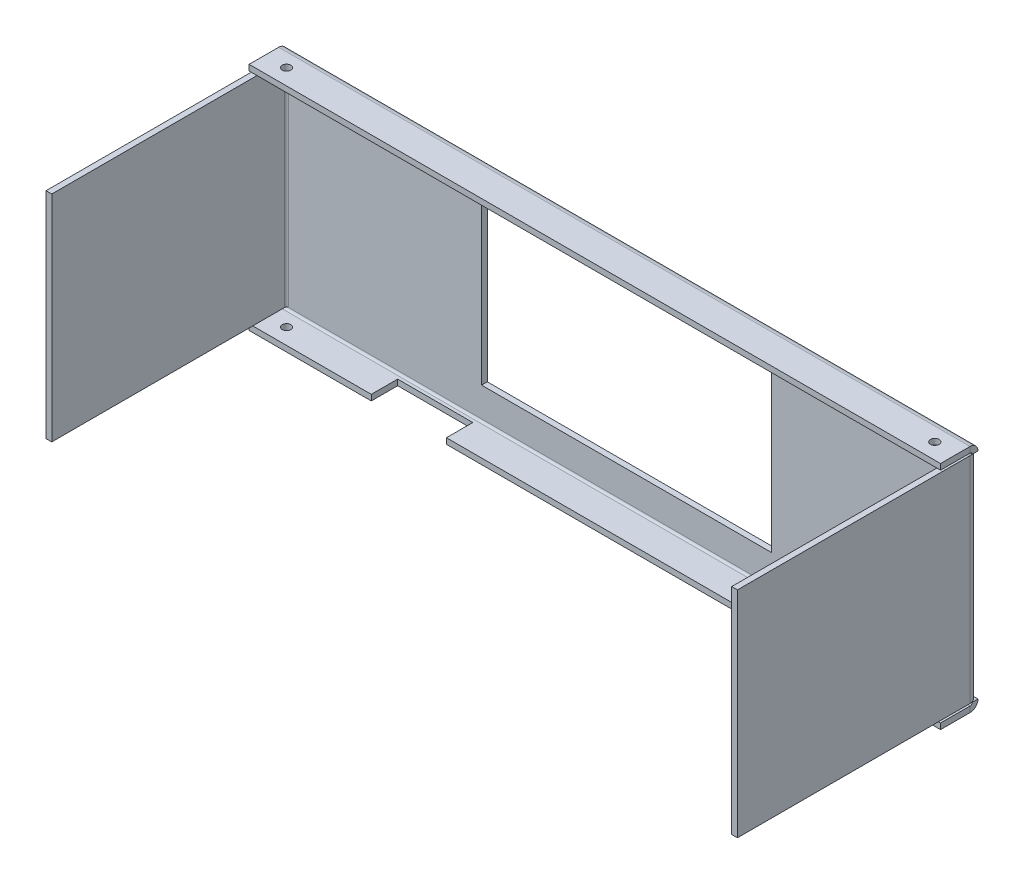
SolidWorks part; units mm, degrees
note: The reader was unsure of these and kept them because the rebuilt part matched: flange length of "Edge-Flange1", "Edge-Flange2".
ref_plane "Front Plane" through (0, 0, 0) normal (0, 0, 1) x (1, 0, 0)
ref_plane "Top Plane" through (0, 0, 0) normal (0, 1, 0) x (1, 0, 0)
ref_plane "Right Plane" through (0, 0, 0) normal (1, 0, 0) x (0, 0, -1)
sketch "Sketch1" plane through (0, 0, 0) normal (0, 0, 1) x (1, 0, 0)
  line L1 (-120, 40) -> (120, 40)
  line L2 (-120, 40) -> (-120, -40)
  line L3 (-120, -40) -> (120, -40)
  line L4 (120, 40) -> (120, -40)
  line L5 (-120, 40) -> (120, -40) construction
  line L6 (-120, -40) -> (120, 40) construction
  point P0 (0, 0)
  dimension "D1" = 240
  dimension "D2" = 80
sketch "Sketch19" plane through (0, 40, 0) normal (0, 1, 0) x (1, 0, 0)
  line L0 (120, -6.5) -> (112.5, -6.5)
  line L1 (120, 0) -> (120, -13) construction
  line L2 (112.5, 0) -> (112.5, -5.5)
  line L3 (-120, 0) -> (118, 0) construction
  circle A0 centre (112.5, -5.5) radius 1.5
  dimension "D2" = 3
  dimension "D1" = 7.5
sketch "Sketch20" plane through (0, 40, 0) normal (0, 1, 0) x (1, 0, 0)
  line L0 (0, 0) -> (0, -13) construction
  line L1 (120, -13) -> (-120, -13) construction
sketch "Sketch25" plane through (0, -38, 0) normal (0, 1, 0) x (1, 0, 0)
  line L1 (-80, 0) -> (-54, 0)
  line L2 (-80, 0) -> (-80, -13)
  line L3 (-80, -13) -> (-54, -13)
  line L4 (-54, 0) -> (-54, -13)
  dimension "D1" = 13
sketch "Sketch29" plane through (0, -38, 0) normal (0, 1, 0) x (1, 0, 0)
  line L0 (-80, -0.2803) -> (-53.9351, -0.2803)
  line L2 (-80, -0.2803) -> (-54, -0.2803)
  line L3 (-80, -0.2803) -> (-80, -13)
  line L4 (-80, -13) -> (-54, -13)
  line L5 (-54, -0.2803) -> (-54, -13)
sketch "Sketch30" plane through (0, 0, 0) normal (0, 0, 1) x (1, 0, 0)
  line L0 (-0.8839, -38) -> (-0.8839, 4.8816)
  line L1 (-80, -38) -> (-54, -38)
  line L2 (-80, -38) -> (-80, -36.4813)
  line L3 (-80, -36.4813) -> (-54, -36.4813)
  line L4 (-54, -38) -> (-54, -36.4813)
  line L6 (-51.2062, 31.9731) -> (49.4384, 31.9731)
  line L7 (-51.2062, 31.9731) -> (-51.2062, -22.2099)
  line L8 (-51.2062, -22.2099) -> (49.4384, -22.2099)
  line L9 (49.4384, 31.9731) -> (49.4384, -22.2099)
  line L10 (-51.2062, 31.9731) -> (49.4384, -22.2099) construction
  line L11 (-51.2062, -22.2099) -> (49.4384, 31.9731) construction
sketch "Sketch31" plane through (0, 0, 0) normal (0, 0, 1) x (1, 0, 0)
  line L1 (-120.8839, 44.8816) -> (119.1161, 44.8816)
  line L2 (-120.8839, 44.8816) -> (-120.8839, -35.1184)
  line L3 (-120.8839, -35.1184) -> (119.1161, -35.1184)
  line L4 (119.1161, 44.8816) -> (119.1161, -35.1184)
  line L5 (-120.8839, 44.8816) -> (119.1161, -35.1184) construction
  line L6 (-120.8839, -35.1184) -> (119.1161, 44.8816) construction
  point P0 (-0.8839, 4.8816)
  dimension "D1" = 240
  dimension "D2" = 80
base flange "Base-Flange1" sketch "Sketch31" thickness 2 reverse thickness direction no parameters "D1"=0.7366
edge flange "Edge-Flange1" sketch "Sketch42" flange profiles "Sketch42", "Sketch43" flange angle 90 flange length 13 flange position material inside bend radius 0.7366 thickness 2 relief rectangular parameters "D6"=10, "D8"=1
sketch "Sketch42" plane through (0, 44.8816, 0) normal (0, 1, 0) x (-1, 0, 0)
  line L0 (-119.1161, 0) -> (120.8839, 0) construction
  line L1 (-119.1161, 0) -> (120.8839, 0)
  line L2 (-119.1161, 0) -> (-119.1161, 11)
  line L3 (-119.1161, 11) -> (120.8839, 11)
  line L4 (120.8839, 11) -> (120.8839, 0)
sketch "Sketch43" plane through (0, -35.1184, 0) normal (0, -1, 0) x (1, 0, 0)
  line L0 (-120.8839, 0) -> (119.1161, 0) construction
  line L1 (-120.8839, 0) -> (119.1161, 0)
  line L2 (-120.8839, 0) -> (-120.8839, 11)
  line L3 (-120.8839, 11) -> (119.1161, 11)
  line L4 (119.1161, 11) -> (119.1161, 0)
bend "EdgeBend1" bend radius 0.7366 bend angle 90 parameters "D5"=1
bend "EdgeBend2" bend radius 0.7366 bend angle 90 parameters "D5"=2
edge flange "Edge-Flange2" sketch "Sketch48" flange profiles "Sketch48", "Sketch49" flange angle 90 flange length 83.5 flange position material inside bend radius 0.7366 thickness 2 relief none parameters "D6"=10, "D8"=1
sketch "Sketch48" plane through (-120.8839, 0, 0) normal (-1, 0, 0) x (0, -1, 0)
  line L2 (-42.145, 0) -> (-42.145, 81.5)
  line L3 (-42.145, 81.5) -> (32.3818, 81.5)
  line L4 (32.3818, 81.5) -> (32.3818, 0)
  line L7 (-42.145, 0) -> (32.3818, 0) construction
  line L8 (-42.145, 0) -> (32.3818, 0)
sketch "Sketch49" plane through (119.1161, 0, 0) normal (1, 0, 0) x (0, 1, 0)
  line L0 (-32.3818, 0) -> (42.145, 0) construction
  line L1 (-32.3818, 0) -> (42.145, 0)
  line L2 (-32.3818, 0) -> (-32.3818, 81.5)
  line L3 (-32.3818, 81.5) -> (42.145, 81.5)
  line L4 (42.145, 81.5) -> (42.145, 0)
bend "EdgeBend3" bend radius 0.7366 bend angle 90 parameters "D5"=3
bend "EdgeBend4" bend radius 0.7366 bend angle 90 parameters "D5"=4
sketch "Sketch50" plane through (0, 44.8816, 0) normal (0, 1, 0) x (1, 0, 0)
  line L0 (-120.8839, -11) -> (-113.3839, -11)
  line L1 (-120.8839, -11) -> (119.1161, -11) construction
  line L2 (-113.3839, -11) -> (-113.3839, -3.5)
  circle A0 centre (-113.3839, -3.5) radius 1.5
  dimension "D1" = 7.5
  dimension "D2" = 7.5
sketch "Sketch52" plane through (0, -33.1184, 0) normal (0, 1, 0) x (1, 0, 0)
  line L1 (-78.4829, -1.8352) -> (-52.3962, -1.8352)
  line L2 (-78.4829, -1.8352) -> (-78.4829, -10.9508)
  line L3 (-78.4829, -10.9508) -> (-52.3962, -10.9508)
  line L4 (-52.3962, -1.8352) -> (-52.3962, -10.9508)
extrude "Cut-Extrude2" cut sketch "Sketch52" against normal blind 10 normal cut yes
sketch "Sketch53" plane through (0, -33.1184, 0) normal (0, 1, 0) x (1, 0, 0)
  line L0 (119.1161, -11) -> (-120.8839, -11) construction
  line L1 (-52.3962, -11) -> (-78.4829, -11)
  line L2 (-52.3962, -11) -> (-52.3962, -10.9508)
  line L3 (-52.3962, -10.9508) -> (-78.4829, -10.9508)
  line L4 (-78.4829, -11) -> (-78.4829, -10.9508)
extrude "Cut-Extrude3" cut sketch "Sketch53" against normal blind 10 normal cut yes
sketch "Sketch54" plane through (0, 0, 0) normal (0, 1, 0) x (1, 0, 0)
  line L1 (51.7628, -13.4888) -> (77.8488, -13.4888)
  line L2 (51.7628, -13.4888) -> (51.7628, -13.5427)
  line L3 (51.7628, -13.5427) -> (77.8488, -13.5427)
  line L4 (77.8488, -13.4888) -> (77.8488, -13.5427)
mirror "Mirror3" about plane through (0, 0, 0) normal (1, 0, 0) of "Cut-Extrude3"
sketch "Sketch55" plane through (0, 0, 0) normal (0, 0, 1) x (1, 0, 0)
  line L1 (-51.2062, 31.9731) -> (49.4384, 31.9731)
  line L2 (-51.2062, 31.9731) -> (-51.2062, -22.2099)
  line L3 (-51.2062, -22.2099) -> (49.4384, -22.2099)
  line L4 (49.4384, 31.9731) -> (49.4384, -22.2099)
sketch "Sketch58" plane through (0, 44.8816, 0) normal (0, 1, 0) x (1, 0, 0)
  line L0 (119.1161, -3.5) -> (111.6161, -3.5)
  circle A0 centre (111.6161, -3.5) radius 1.5
  dimension "D1" = 7.5
mirror "Mirror4" about plane through (0, 0, 0) normal (1, 0, 0) of "Cut-Extrude2", "Cut-Extrude3"
sketch "Sketch61" plane through (0, 44.8816, 0) normal (0, 1, 0) x (1, 0, 0)
  line L0 (-113.3839, -3.5) -> (111.6161, -3.5)
  line L2 (111.6161, -0.7366) -> (111.6161, -5.4966)
  line L3 (-120.8839, -0.7366) -> (119.1161, -0.7366) construction
  circle A0 centre (111.6161, -5.4966) radius 1.5
extrude "Cut-Extrude8" cut sketch "Sketch61" against normal through all
sketch "Sketch62" plane through (0, 44.8816, 0) normal (0, 1, 0) x (1, 0, 0)
  line L0 (111.6161, -5.4966) -> (-113.3839, -5.4966)
  circle A0 centre (-113.3839, -5.4966) radius 1.5
  dimension "D1" = 225
extrude "Cut-Extrude9" cut sketch "Sketch62" against normal through all
sketch "Sketch65" plane through (0, 0, 0) normal (0, 0, 1) x (1, 0, 0)
  line L1 (-51.2062, 31.9731) -> (49.4384, 31.9731)
  line L2 (-51.2062, 31.9731) -> (-51.2062, -22.2099)
  line L3 (-51.2062, -22.2099) -> (49.4384, -22.2099)
  line L4 (49.4384, 31.9731) -> (49.4384, -22.2099)
extrude "Cut-Extrude11" cut sketch "Sketch65" against normal through all contours L2 L1 L4 L3 normal cut yes
sketch "Bend-Lines1" [suppressed] plane through (0, 0, 0) normal (0, 1, 0) x (1, 0, 0)
sketch "Bounding-Box1" [suppressed] plane through (0, 0, 0) normal (0, 1, 0) x (1, 0, 0)
sheet metal parameters "Sheet-Metal12" thickness 2 parameters "D1"=0.7366
flat pattern "Flat-Pattern12" [suppressed]
sketch "Bend-Lines2" plane through (0, 0, 0) normal (0, 1, 0) x (1, 0, 0)
sketch3d "Bounding-Box2" [suppressed]
  line L0 (120.8839, -35.1184, 0) -> (-119.1161, -35.1184, 0) construction
  line L1 (120.8839, 44.8816, 0) -> (-119.1161, 44.8816, 0) construction
  line L2 (120.8839, -35.1184, 0) -> (120.8839, 44.8816, 0) construction
  line L3 (-119.1161, -35.1184, 0) -> (-119.1161, 44.8816, 0) construction
sheet metal parameters "Sheet-Metal13" thickness 2 parameters "D1"=0.7366
flat pattern "Flat-Pattern12"
sketch "Bend-Lines2" plane through (0, 0, 0) normal (0, 0, 1) x (1, 0, 0)
  line L0 (-120.8839, -33.7457) -> (119.1161, -33.7457) construction
  line L1 (119.1161, 43.5089) -> (-120.8839, 43.5089) construction
  line L2 (-120.8839, -33.7457) -> (119.1161, -33.7457) construction
  line L3 (119.1161, 43.5089) -> (-120.8839, 43.5089) construction
sketch3d "Bounding-Box2" [suppressed]
  line L0 (-120.8839, -45.373, 0) -> (119.1161, -45.373, 0) construction
  line L1 (-120.8839, 55.1363, 0) -> (119.1161, 55.1363, 0) construction
  line L2 (-120.8839, -45.373, 0) -> (-120.8839, 55.1363, 0) construction
  line L3 (119.1161, -45.373, 0) -> (119.1161, 55.1363, 0) construction
bend of the flat pattern "Flatten-<EdgeBend1>1"
bend of the flat pattern "Flatten-<EdgeBend2>1"
sheet metal parameters "Sheet-Metal14" thickness 2 parameters "D1"=0.7366
flat pattern "Flat-Pattern12"
sketch "Bend-Lines2" plane through (0, 0, 0) normal (0, 0, 1) x (1, 0, 0)
  line L0 (-120.8839, -33.7457) -> (119.1161, -33.7457) construction
  line L1 (119.1161, 43.5089) -> (-120.8839, 43.5089) construction
  line L2 (-120.8839, -33.7457) -> (119.1161, -33.7457) construction
  line L3 (119.1161, 43.5089) -> (-120.8839, 43.5089) construction
  line L4 (117.7434, -32.3818) -> (117.7434, 42.145) construction
  line L5 (-119.5112, 42.145) -> (-119.5112, -32.3818) construction
  line L6 (117.7434, -32.3818) -> (117.7434, 42.145) construction
  line L7 (-119.5112, 42.145) -> (-119.5112, -32.3818) construction
sketch3d "Bounding-Box2" [suppressed]
  line L0 (-203.1386, -45.373, 0) -> (201.3707, -45.373, 0) construction
  line L1 (-203.1386, 55.1363, 0) -> (201.3707, 55.1363, 0) construction
  line L2 (-203.1386, -45.373, 0) -> (-203.1386, 55.1363, 0) construction
  line L3 (201.3707, -45.373, 0) -> (201.3707, 55.1363, 0) construction
bend of the flat pattern "Flatten-<EdgeBend1>1"
bend of the flat pattern "Flatten-<EdgeBend2>1"
bend of the flat pattern "Flatten-<EdgeBend3>1"
bend of the flat pattern "Flatten-<EdgeBend4>1"
sheet metal parameters "Sheet-Metal16" thickness 2 parameters "D1"=0.7366
flat pattern "Flat-Pattern12"
sketch "Bend-Lines2" plane through (0, 0, 0) normal (0, 0, 1) x (1, 0, 0)
  line L0 (-120.8839, -33.7457) -> (119.1161, -33.7457) construction
  line L1 (119.1161, 43.5089) -> (-120.8839, 43.5089) construction
  line L2 (-120.8839, -33.7457) -> (119.1161, -33.7457) construction
  line L3 (119.1161, 43.5089) -> (-120.8839, 43.5089) construction
  line L4 (117.7434, -32.3818) -> (117.7434, 42.145) construction
  line L5 (-119.5112, 42.145) -> (-119.5112, -32.3818) construction
  line L6 (117.7434, -32.3818) -> (117.7434, 42.145) construction
  line L7 (-119.5112, 42.145) -> (-119.5112, -32.3818) construction
sketch3d "Bounding-Box2" [suppressed]
  line L0 (-203.1386, -45.373, 0) -> (201.3707, -45.373, 0) construction
  line L1 (-203.1386, 55.1363, 0) -> (201.3707, 55.1363, 0) construction
  line L2 (-203.1386, -45.373, 0) -> (-203.1386, 55.1363, 0) construction
  line L3 (201.3707, -45.373, 0) -> (201.3707, 55.1363, 0) construction
bend of the flat pattern "Flatten-<EdgeBend1>1"
bend of the flat pattern "Flatten-<EdgeBend2>1"
bend of the flat pattern "Flatten-<EdgeBend3>1"
bend of the flat pattern "Flatten-<EdgeBend4>1"
sheet metal parameters "Sheet-Metal18" thickness 2 parameters "D1"=0.7366
flat pattern "Flat-Pattern12"
sketch "Bend-Lines2" plane through (0, 0, 0) normal (0, 0, 1) x (1, 0, 0)
  line L0 (-120.8839, -33.7457) -> (119.1161, -33.7457) construction
  line L1 (119.1161, 43.5089) -> (-120.8839, 43.5089) construction
  line L2 (-120.8839, -33.7457) -> (119.1161, -33.7457) construction
  line L3 (119.1161, 43.5089) -> (-120.8839, 43.5089) construction
  line L4 (117.7434, -32.3818) -> (117.7434, 42.145) construction
  line L5 (-119.5112, 42.145) -> (-119.5112, -32.3818) construction
  line L6 (117.7434, -32.3818) -> (117.7434, 42.145) construction
  line L7 (-119.5112, 42.145) -> (-119.5112, -32.3818) construction
sketch3d "Bounding-Box2" [suppressed]
  line L0 (-203.1386, -45.373, 0) -> (201.3707, -45.373, 0) construction
  line L1 (-203.1386, 55.1363, 0) -> (201.3707, 55.1363, 0) construction
  line L2 (-203.1386, -45.373, 0) -> (-203.1386, 55.1363, 0) construction
  line L3 (201.3707, -45.373, 0) -> (201.3707, 55.1363, 0) construction
bend of the flat pattern "Flatten-<EdgeBend1>1"
bend of the flat pattern "Flatten-<EdgeBend2>1"
bend of the flat pattern "Flatten-<EdgeBend3>1"
bend of the flat pattern "Flatten-<EdgeBend4>1"
sheet metal parameters "Sheet-Metal20" thickness 2 parameters "D1"=0.7366
flat pattern "Flat-Pattern12"
sketch "Bend-Lines2" plane through (0, 0, 0) normal (0, 0, 1) x (1, 0, 0)
  line L0 (-120.8839, -33.7457) -> (119.1161, -33.7457) construction
  line L1 (119.1161, 43.5089) -> (-120.8839, 43.5089) construction
  line L2 (-120.8839, -33.7457) -> (119.1161, -33.7457) construction
  line L3 (119.1161, 43.5089) -> (-120.8839, 43.5089) construction
  line L4 (117.7434, -32.3818) -> (117.7434, 42.145) construction
  line L5 (-119.5112, 42.145) -> (-119.5112, -32.3818) construction
  line L6 (117.7434, -32.3818) -> (117.7434, 42.145) construction
  line L7 (-119.5112, 42.145) -> (-119.5112, -32.3818) construction
sketch3d "Bounding-Box2" [suppressed]
  line L0 (-203.1386, -45.373, 0) -> (201.3707, -45.373, 0) construction
  line L1 (-203.1386, 55.1363, 0) -> (201.3707, 55.1363, 0) construction
  line L2 (-203.1386, -45.373, 0) -> (-203.1386, 55.1363, 0) construction
  line L3 (201.3707, -45.373, 0) -> (201.3707, 55.1363, 0) construction
bend of the flat pattern "Flatten-<EdgeBend1>1"
bend of the flat pattern "Flatten-<EdgeBend2>1"
bend of the flat pattern "Flatten-<EdgeBend3>1"
bend of the flat pattern "Flatten-<EdgeBend4>1"
sheet metal parameters "Sheet-Metal23" thickness 2 parameters "D1"=0.7366
flat pattern "Flat-Pattern12" [suppressed]
sketch "Bend-Lines2" plane through (0, 0, 0) normal (0, 0, 1) x (1, 0, 0)
  line L0 (-120.8839, -33.7457) -> (119.1161, -33.7457) construction
  line L1 (119.1161, 43.5089) -> (-120.8839, 43.5089) construction
  line L2 (-120.8839, -33.7457) -> (119.1161, -33.7457) construction
  line L3 (119.1161, 43.5089) -> (-120.8839, 43.5089) construction
  line L4 (117.7434, -32.3818) -> (117.7434, 42.145) construction
  line L5 (-119.5112, 42.145) -> (-119.5112, -32.3818) construction
  line L6 (117.7434, -32.3818) -> (117.7434, 42.145) construction
  line L7 (-119.5112, 42.145) -> (-119.5112, -32.3818) construction
sketch3d "Bounding-Box2" [suppressed]
  line L0 (-197.1386, -45.373, 0) -> (195.3707, -45.373, 0) construction
  line L1 (-197.1386, 55.1363, 0) -> (195.3707, 55.1363, 0) construction
  line L2 (-197.1386, -45.373, 0) -> (-197.1386, 55.1363, 0) construction
  line L3 (195.3707, -45.373, 0) -> (195.3707, 55.1363, 0) construction
bend of the flat pattern "Flatten-<EdgeBend1>1"
bend of the flat pattern "Flatten-<EdgeBend2>1"
bend of the flat pattern "Flatten-<EdgeBend3>1"
bend of the flat pattern "Flatten-<EdgeBend4>1"
sketch "Sketch58-1" [suppressed] plane through (0, 44.1363, -2) normal (0, 0, -1) x (1, 0, 0)
  line L0 (119.1161, -3.5) -> (111.6161, -3.5)
  circle A0 centre (111.6161, -3.5) radius 1.5
  dimension "D1" = 7.5
sheet metal parameters "Sheet-Metal24" thickness 2 parameters "D1"=0.7366
flat pattern "Flat-Pattern12" [suppressed]
sketch "Bend-Lines2" plane through (0, 0, 0) normal (0, 0, 1) x (1, 0, 0)
  line L0 (-120.8839, -33.7457) -> (119.1161, -33.7457) construction
  line L1 (119.1161, 43.5089) -> (-120.8839, 43.5089) construction
  line L2 (-120.8839, -33.7457) -> (119.1161, -33.7457) construction
  line L3 (119.1161, 43.5089) -> (-120.8839, 43.5089) construction
  line L4 (117.7434, -32.3818) -> (117.7434, 42.145) construction
  line L5 (-119.5112, 42.145) -> (-119.5112, -32.3818) construction
  line L6 (117.7434, -32.3818) -> (117.7434, 42.145) construction
  line L7 (-119.5112, 42.145) -> (-119.5112, -32.3818) construction
sketch3d "Bounding-Box2" [suppressed]
  line L0 (-197.1386, -45.373, 0) -> (195.3707, -45.373, 0) construction
  line L1 (-197.1386, 55.1363, 0) -> (195.3707, 55.1363, 0) construction
  line L2 (-197.1386, -45.373, 0) -> (-197.1386, 55.1363, 0) construction
  line L3 (195.3707, -45.373, 0) -> (195.3707, 55.1363, 0) construction
bend of the flat pattern "Flatten-<EdgeBend1>1"
bend of the flat pattern "Flatten-<EdgeBend2>1"
bend of the flat pattern "Flatten-<EdgeBend3>1"
bend of the flat pattern "Flatten-<EdgeBend4>1"
sketch "Sketch58-1" [suppressed] plane through (0, 44.1363, -2) normal (0, 0, -1) x (1, 0, 0)
  line L0 (119.1161, -3.5) -> (111.6161, -3.5)
  circle A0 centre (111.6161, -3.5) radius 1.5
  dimension "D1" = 7.5
sketch "Sketch50-1" [suppressed] plane through (0, 44.1363, -2) normal (0, 0, -1) x (1, 0, 0)
  line L0 (-120.8839, -11) -> (-113.3839, -11)
  line L2 (-113.3839, -11) -> (-113.3839, -3.5)
  circle A0 centre (-113.3839, -3.5) radius 1.5
  dimension "D1" = 7.5
  dimension "D2" = 7.5
sketch "Sketch62-1" [suppressed] plane through (0, 44.1363, -2) normal (0, 0, -1) x (1, 0, 0)
  line L0 (111.6161, -5.4966) -> (-113.3839, -5.4966)
  dimension "D1" = 225
sheet metal parameters "Sheet-Metal25" thickness 2 parameters "D1"=0.7366
flat pattern "Flat-Pattern12" [suppressed]
sketch "Bend-Lines2" plane through (0, 0, 0) normal (0, 0, 1) x (1, 0, 0)
  line L0 (-120.8839, -33.7457) -> (119.1161, -33.7457) construction
  line L1 (119.1161, 43.5089) -> (-120.8839, 43.5089) construction
  line L2 (-120.8839, -33.7457) -> (119.1161, -33.7457) construction
  line L3 (119.1161, 43.5089) -> (-120.8839, 43.5089) construction
  line L4 (117.7434, -32.3818) -> (117.7434, 42.145) construction
  line L5 (-119.5112, 42.145) -> (-119.5112, -32.3818) construction
  line L6 (117.7434, -32.3818) -> (117.7434, 42.145) construction
  line L7 (-119.5112, 42.145) -> (-119.5112, -32.3818) construction
sketch3d "Bounding-Box2" [suppressed]
  line L0 (-197.1386, -45.373, 0) -> (195.3707, -45.373, 0) construction
  line L1 (-197.1386, 55.1363, 0) -> (195.3707, 55.1363, 0) construction
  line L2 (-197.1386, -45.373, 0) -> (-197.1386, 55.1363, 0) construction
  line L3 (195.3707, -45.373, 0) -> (195.3707, 55.1363, 0) construction
bend of the flat pattern "Flatten-<EdgeBend1>1"
bend of the flat pattern "Flatten-<EdgeBend2>1"
bend of the flat pattern "Flatten-<EdgeBend3>1"
bend of the flat pattern "Flatten-<EdgeBend4>1"
sketch "Sketch58-1" [suppressed] plane through (0, 44.1363, -2) normal (0, 0, -1) x (1, 0, 0)
  line L0 (119.1161, -3.5) -> (111.6161, -3.5)
  circle A0 centre (111.6161, -3.5) radius 1.5
  dimension "D1" = 7.5
sketch "Sketch50-1" [suppressed] plane through (0, 44.1363, -2) normal (0, 0, -1) x (1, 0, 0)
  line L0 (-120.8839, -11) -> (-113.3839, -11)
  line L2 (-113.3839, -11) -> (-113.3839, -3.5)
  circle A0 centre (-113.3839, -3.5) radius 1.5
  dimension "D1" = 7.5
  dimension "D2" = 7.5
sketch "Sketch62-1" [suppressed] plane through (0, 44.1363, -2) normal (0, 0, -1) x (1, 0, 0)
  line L0 (111.6161, -5.4966) -> (-113.3839, -5.4966)
  circle A0 centre (-113.3839, -5.4966) radius 1.5
  dimension "D1" = 225
sheet metal parameters "Sheet-Metal27" thickness 2 parameters "D1"=0.7366
flat pattern "Flat-Pattern12" [suppressed]
sketch "Bend-Lines2" plane through (0, 0, 0) normal (0, 0, 1) x (1, 0, 0)
  line L0 (-120.8839, -33.7457) -> (119.1161, -33.7457) construction
  line L1 (119.1161, 43.5089) -> (-120.8839, 43.5089) construction
  line L2 (-120.8839, -33.7457) -> (119.1161, -33.7457) construction
  line L3 (119.1161, 43.5089) -> (-120.8839, 43.5089) construction
  line L4 (117.7434, -32.3818) -> (117.7434, 42.145) construction
  line L5 (-119.5112, 42.145) -> (-119.5112, -32.3818) construction
  line L6 (117.7434, -32.3818) -> (117.7434, 42.145) construction
  line L7 (-119.5112, 42.145) -> (-119.5112, -32.3818) construction
sketch3d "Bounding-Box2" [suppressed]
  line L0 (-201.6386, -45.373, 0) -> (199.8707, -45.373, 0) construction
  line L1 (-201.6386, 55.1363, 0) -> (199.8707, 55.1363, 0) construction
  line L2 (-201.6386, -45.373, 0) -> (-201.6386, 55.1363, 0) construction
  line L3 (199.8707, -45.373, 0) -> (199.8707, 55.1363, 0) construction
bend of the flat pattern "Flatten-<EdgeBend1>1"
bend of the flat pattern "Flatten-<EdgeBend2>1"
bend of the flat pattern "Flatten-<EdgeBend3>1"
bend of the flat pattern "Flatten-<EdgeBend4>1"
sketch "Sketch58-1" [suppressed] plane through (0, 44.1363, -2) normal (0, 0, -1) x (1, 0, 0)
  line L0 (119.1161, -3.5) -> (111.6161, -3.5)
  circle A0 centre (111.6161, -3.5) radius 1.5
  dimension "D1" = 7.5
sketch "Sketch50-1" [suppressed] plane through (0, 44.1363, -2) normal (0, 0, -1) x (1, 0, 0)
  line L0 (-120.8839, -11) -> (-113.3839, -11)
  line L2 (-113.3839, -11) -> (-113.3839, -3.5)
  circle A0 centre (-113.3839, -3.5) radius 1.5
  dimension "D1" = 7.5
  dimension "D2" = 7.5
sketch "Sketch62-1" [suppressed] plane through (0, 44.1363, -2) normal (0, 0, -1) x (1, 0, 0)
  line L0 (111.6161, -5.4966) -> (-113.3839, -5.4966)
  circle A0 centre (-113.3839, -5.4966) radius 1.5
  dimension "D1" = 225
